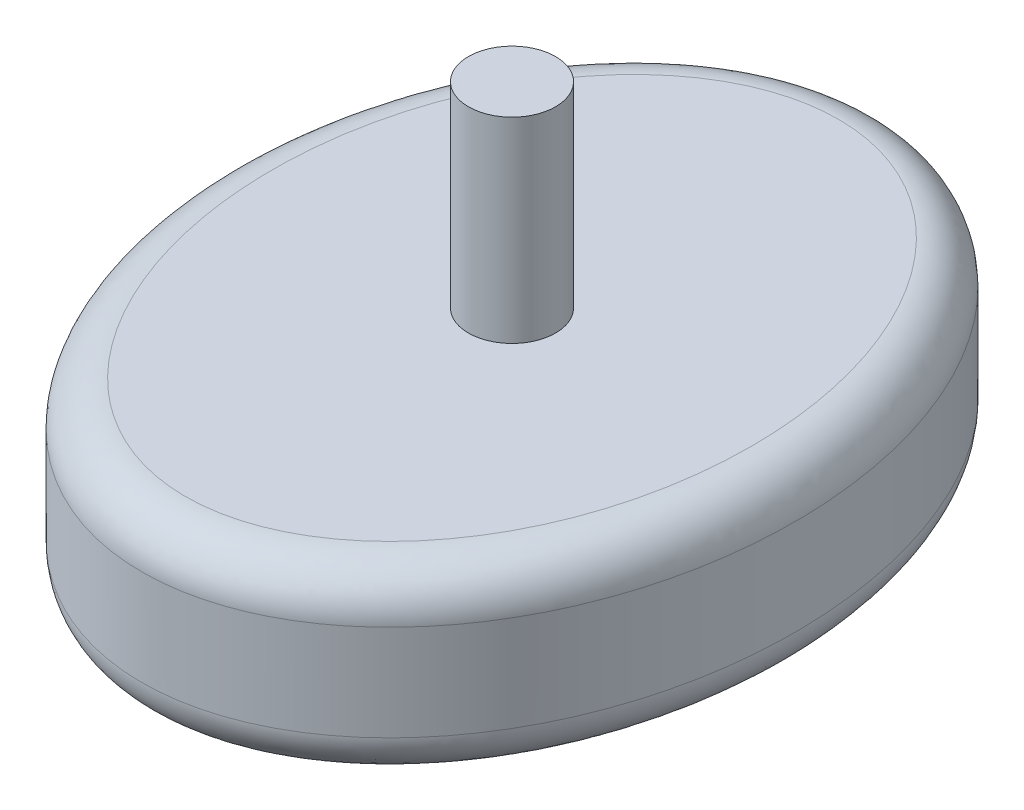
SolidWorks part; units mm, degrees
ref_plane "Front Plane" through (0, 0, 0) normal (0, 0, 1) x (1, 0, 0)
ref_plane "Top Plane" through (0, 0, 0) normal (0, 1, 0) x (1, 0, 0)
ref_plane "Right Plane" through (0, 0, 0) normal (1, 0, 0) x (0, 0, -1)
sketch "Sketch1" plane through (0, 0, 0) normal (0, 1, 0) x (1, 0, 0)
  line L0 (-6.5, 0) -> (6.5, 0) construction
  circle A6 centre (0, 0) radius 2.5
  ellipse E0 centre (0, 0) end of major axis (0, 8.5) minor radius 6.5
  dimension "D1" = 5
  dimension "D2" = 13
  dimension "D3" = 17
extrude "Boss-Extrude1" add sketch "Sketch1" along normal blind 3.2
sketch "Sketch2" plane through (0, 3.2, 0) normal (0, 1, 0) x (1, 0, 0)
  ellipse E0 centre (0, 0) end of major axis (0, 8.5) minor radius 6.5
  ellipse E1 centre (0, 0) end of major axis (0, 8.5) minor radius 6.5 construction
extrude "Boss-Extrude2" add sketch "Sketch2" along normal blind 1
fillet "Fillet1" radius 1 2 edges at (0, 0, -8.5) (0, 4.2, -8.5)
sketch "Sketch3" plane through (0, 4.2, 0) normal (0, 1, 0) x (1, 0, 0)
  circle A0 centre (0, 0) radius 1
  dimension "D1" = 2
extrude "Boss-Extrude3" add sketch "Sketch3" along normal blind 4.5
